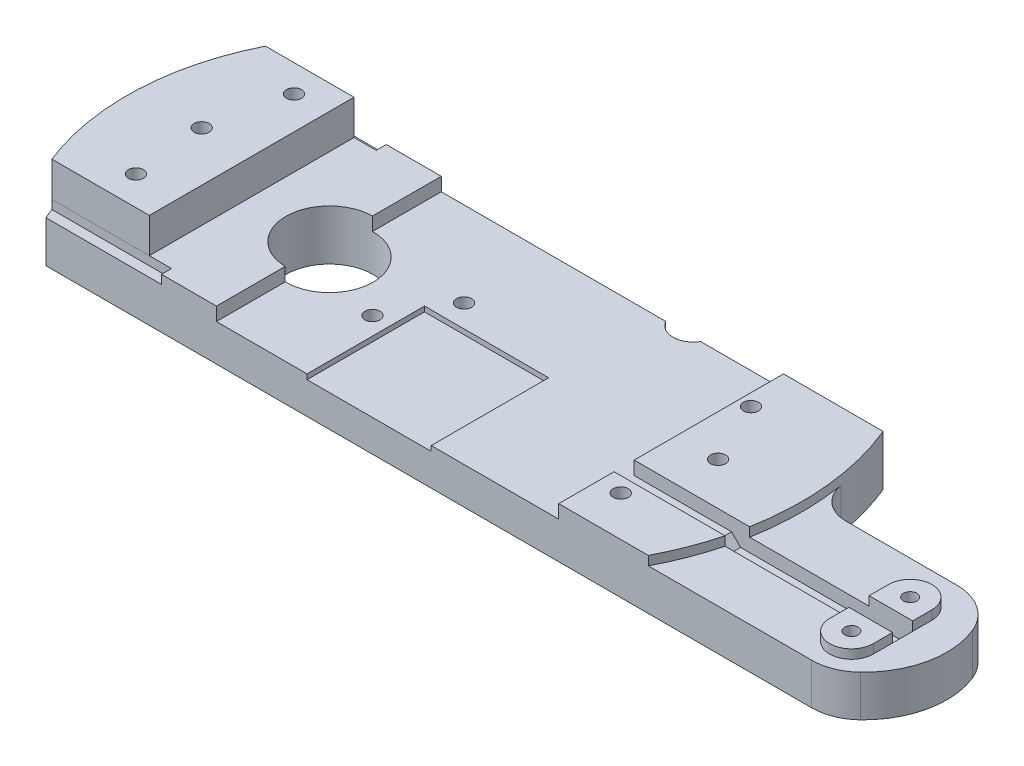
SolidWorks part; units mm, degrees
material "1060 Alloy"
ref_plane "Front Plane" through (0, 0, 0) normal (0, 0, 1) x (1, 0, 0)
ref_plane "Top Plane" through (0, 0, 0) normal (0, 1, 0) x (1, 0, 0)
ref_plane "Right Plane" through (0, 0, 0) normal (1, 0, 0) x (0, 0, -1)
sketch "Sketch1" plane through (0, 0, 0) normal (0, 1, 0) x (1, 0, 0)
  line L1 (-97.5, -33.5) -> (97.5, -33.5)
  line L2 (-97.5, -33.5) -> (-97.5, 33.5)
  line L3 (-97.5, 33.5) -> (97.5, 33.5)
  line L4 (97.5, -33.5) -> (97.5, 33.5)
  line L5 (-97.5, -33.5) -> (97.5, 33.5) construction
  line L6 (-97.5, 33.5) -> (97.5, -33.5) construction
  point P0 (0, 0)
  dimension "D1" = 67
  dimension "D2" = 195
extrude "Boss-Extrude1" add sketch "Sketch1" along normal blind 25.4
sketch "Sketch2" plane through (0, 0, 0) normal (0, -1, 0) x (1, 0, 0)
  line L0 (-97.5, -33.5) -> (-97.5, 33.5) construction
  line L1 (97.5, 33.5) -> (97.5, -33.5) construction
  line L2 (97.5, 33.5) -> (88.5, 33.5)
  line L3 (-97.5, 33.5) -> (97.5, 33.5) construction
  line L4 (97.5, -33.5) -> (91.5, -33.5)
  line L5 (97.5, -33.5) -> (-97.5, -33.5) construction
  line L6 (-97.5, 33.5) -> (-91, 33.5)
  line L7 (-97.5, -33.5) -> (-88, -33.5)
  circle A0 centre (18.0922, -3.2198) radius 79.4078
  circle A1 centre (-22.6589, 2.9929) radius 74.8411
  line M7 (97.5, -33.5) -> (97.5, 33.5)
  line M8 (97.5, 33.5) -> (-97.5, 33.5)
  line M9 (-97.5, 33.5) -> (-97.5, -33.5)
  line M10 (-97.5, -33.5) -> (97.5, -33.5)
  dimension "D1" = 9
  dimension "D2" = 6
  dimension "D3" = 6.5
  dimension "D4" = 9.5
extrude "Cut-Extrude1" cut sketch "Sketch2" against normal through all contours A0 M7 M8 | A0 M10 M7 | A1 M9 M10 | A1 M8 M9 region at (94.8284, 0, 24.4273) region at (95.7123, 0, -25.9883) region at (-95.5654, 0, 25.941) region at (-94.6839, 0, -24.4966)
sketch "Sketch3" plane through (0, 0, 33.5) normal (0, 0, -1) x (-1, 0, 0)
  line L0 (97.5, 25.4) -> (63.2, 25.4)
  line L2 (63.2, 25.4) -> (63.2, 15)
  line L3 (63.2, 15) -> (40.2, 15)
  line L4 (40.2, 15) -> (40.2, 11)
  line L5 (40.2, 11) -> (-61.8, 11)
  line L6 (-91.5, 25.4) -> (88, 25.4) construction
  line L10 (97.5, 0) -> (97.5, 25.4) construction
  line L11 (-61.8, 11) -> (-61.8, 15)
  line L12 (-61.8, 15) -> (-97.5, 15)
  line L13 (-97.5, 25.4) -> (-97.5, 0) construction
  line L14 (-97.5, 15) -> (-97.5, 25.4)
  line L15 (-97.5, 25.4) -> (63.2, 25.4)
  line M13 (-88.5, 0) -> (-88.5, 25.4)
  line M14 (-88.5, 25.4) -> (91, 25.4)
  dimension "D1" = 10.4
  dimension "D2" = 34.3
  dimension "D3" = 23
  dimension "D4" = 4
  dimension "D5" = 102
extrude "Cut-Extrude2" cut sketch "Sketch3" along normal through all contours L11 L12 L2 L3 L4 L5 M13 M14 | L2 L3 L4 L5 L11 L12 L14 L15 region at (12.2699, 18.7206, 33.5)
sketch "Sketch4" plane through (0, 25.4, 0) normal (0, 1, 0) x (1, 0, 0)
  line L0 (-56.5873, 33.5) -> (-56.5873, 30.5)
  line L1 (-63.2, 33.5) -> (-88, 33.5) construction
  line L2 (-56.5873, 30.5) -> (-89.5873, 30.5)
  line L3 (-56.5873, -33.5) -> (-56.5873, -30.5)
  line L4 (-91, -33.5) -> (-63.2, -33.5) construction
  line L5 (-56.5873, -30.5) -> (-92.2617, -30.5)
  line L6 (-56.5873, 33.5) -> (-63.2, 33.5)
  line L7 (-56.5873, -33.5) -> (-63.2, -33.5)
  arc A0 (-88, 33.5) -> (-91, -33.5) centre (-22.6589, -2.9929) ccw construction
  line M5 (-91, -33.5) -> (-63.2, -33.5)
  line M6 (-63.2, -33.5) -> (-63.2, 33.5)
  line M7 (-63.2, 33.5) -> (-88, 33.5)
  arc M8 (-88, 33.5) -> (-91, -33.5) centre (-22.6589, -2.9929) ccw
  dimension "D1" = 3
  dimension "D2" = 3
  dimension "D3" = 33
extrude "Cut-Extrude3" cut sketch "Sketch4" against normal blind 13 contours L2 M6 M7 M8 | L0 L6 L2 M6 | L5 M6 M8 M5 | L7 L3 L5 M6 region at (-59.8937, 25.4, -32) region at (-76.0082, 25.4, -31.9845) region at (-77.4242, 25.4, 31.9889) region at (-59.8937, 25.4, 32)
sketch "Sketch6" plane through (0, 0, 0) normal (0, -1, 0) x (1, 0, 0)
  line L0 (-63.2, -33.5) -> (-97.5, -33.5)
  line L1 (91.5, -33.5) -> (-88, -33.5) construction
  line L2 (-63.2, -33.5) -> (-63.2, 33.5)
  line L3 (-91, 33.5) -> (88.5, 33.5) construction
  line L4 (-63.2, -9) -> (-28.1, -9) construction
  line L5 (-63.2, 8.7) -> (-18.5, 8.7) construction
  line L6 (-63.2, -8.2) -> (-8.1, -8.2) construction
  line L8 (91.5, -33.5) -> (-88, -33.5) construction
  line L9 (-97.5, -33.5) -> (-97.5, 33.5)
  line L10 (-97.5, 33.5) -> (-63.2, 33.5)
  circle A1 centre (-18.5, 8.7) radius 2.25
  circle A2 centre (74.1, -1.7) radius 2.25
  circle A3 centre (68.3, 21.5) radius 2.25
  circle A4 centre (65.4, -20.2) radius 2.25
  circle A5 centre (-8.1, -8.2) radius 2.25
  circle A6 centre (-75.9, 21.8) radius 2.25
  circle A7 centre (-78, 0.1) radius 2.25
  circle A8 centre (-73, -22.4) radius 2.25
  arc A10 (-91, 33.5) -> (-88, -33.5) centre (-22.6589, 2.9929) ccw construction
  dimension "D22" = 4.5
  dimension "D3" = 35.1
  dimension "D4" = 34.3
  dimension "D5" = 44.7
  dimension "D6" = 24.5
  dimension "D7" = 55.1
  dimension "D8" = 42.2
  dimension "D9" = 137.3
  dimension "D10" = 128.6
  dimension "D11" = 131.5
  dimension "D12" = 9.8
  dimension "D13" = 14.8
  dimension "D14" = 12.7
  dimension "D15" = 11.1
  dimension "D16" = 33.6
  dimension "D17" = 55.3
  dimension "D18" = 31.8
  dimension "D19" = 55
  dimension "D20" = 13.3
  dimension "D21" = 25.3
extrude "Cut-Extrude4" cut sketch "Sketch6" against normal through all contours A5 | A1 | A6 | A7 | A8 | A4 | A2 | A3 region at (-18.5, 0, 8.7) region at (74.1, 0, -1.7) region at (68.3, 0, 21.5) region at (65.4, 0, -20.2) region at (-8.1, 0, -8.2) region at (-75.9, 0, 21.8) region at (-78, 0, 0.1) region at (-73, 0, -22.4)
sketch "Sketch7" plane through (0, 11, 0) normal (0, 1, 0) x (1, 0, 0)
  line L1 (-13.2, 1.5) -> (23.8, 1.5)
  line L2 (-13.2, 1.5) -> (-13.2, -33.5)
  line L3 (-13.2, -33.5) -> (23.8, -33.5)
  line L4 (23.8, 1.5) -> (23.8, -33.5)
  line L8 (-63.2, 30.5) -> (-63.2, -30.5) construction
  line L9 (-63.2, 30.5) -> (-63.2, -30.5) construction
  line L10 (-40.2, -33.5) -> (61.8, -33.5) construction
  dimension "D1" = 50
  dimension "D2" = 87
  dimension "D3" = 35
extrude "Cut-Extrude5" cut sketch "Sketch7" against normal blind 1.5
sketch "Sketch8" plane through (0, 25.4, 0) normal (0, 1, 0) x (1, 0, 0)
  line L0 (-56.5873, -33.5) -> (-97.5, -33.5)
  line L1 (-97.5, -33.5) -> (-97.5, 33.5)
  line L3 (-97.5, 33.5) -> (31.9, 33.5)
  line L6 (31.9, 36.5) -> (31.9, 30.5)
  line L7 (31.9, 33.5) -> (37.0962, 33.5)
  line L10 (-56.5873, 33.5) -> (-88, 33.5) construction
  line L11 (-40.2, 33.5) -> (61.8, 33.5) construction
  circle A1 centre (31.9, 36.5) radius 6
  arc A2 (-89.5873, 30.5) -> (-92.2617, -30.5) centre (-22.6589, -2.9929) ccw construction
  dimension "D1" = 12
  dimension "D2" = 129.4
extrude "Cut-Extrude6" cut sketch "Sketch8" against normal blind 18.5 contours L6 A1 L7 | L3 A1 L6 region at (29.8648, 25.4, -32.2699) region at (33.9352, 25.4, -32.2699)
sketch "Sketch9" plane through (0, 0, 0) normal (0, -1, 0) x (1, 0, 0)
  line L0 (88.5, 33.5) -> (137.2004, 33.5)
  line L1 (139.5727, -7.5) -> (97.3846, -7.5)
  arc A0 (153.4738, 1.8643) -> (147.5429, 29.3643) centre (130.3054, 11.2571) ccw
  arc A1 (91.5, -33.5) -> (88.5, 33.5) centre (18.0922, -3.2198) ccw construction
  arc A2 (142.3827, -10.6321) -> (147.5429, 29.3643) centre (130.3054, 11.2571) ccw construction
  arc A3 (147.5429, 29.3643) -> (137.2004, 33.5) centre (137.2004, 18.5) ccw
  arc A4 (147.5429, 29.3643) -> (137.9704, 33.4802) centre (137.2004, 18.5) ccw construction
  arc A5 (139.5727, -7.5) -> (153.4738, 1.8643) centre (139.5727, 7.5) ccw
  circle A6 centre (112.8948, -27.5) radius 16 construction
  circle A7 centre (103.4238, 59.4942) radius 16 construction
  circle A8 centre (112.8948, -27.5) radius 20 construction
  arc A9 (97.3846, -7.5) -> (88.5, 33.5) centre (18.0922, -3.2198) ccw
  circle A10 centre (138.3, 5.25) radius 2
  circle A11 centre (138.3, 22.75) radius 2
  circle A12 centre (138.3, 22.75) radius 2 construction
  circle A13 centre (138.3, 5.25) radius 2 construction
  dimension "D1" = 4
extrude "Boss-Extrude2" add sketch "Sketch9" against normal offset from surface (12.3 mm away) 1.3 up to face at (-16.25, 11, 8.7) offset beyond the face yes
fillet "Fillet1" radius 10 1 edges at (97.3846, 6.15, -7.5)
sketch "Sketch10" plane through (0, 0, 0) normal (0, -1, 0) x (1, 0, 0)
  circle A0 centre (-40.0178, 0) radius 13
  dimension "D1" = 26
extrude "Cut-Extrude7" cut sketch "Sketch10" against normal through all
sketch "Sketch11" plane through (0, 12.3, 0) normal (0, 1, 0) x (1, 0, 0)
  line L0 (138.3, -5.25) -> (138.3, -22.75) construction
  line L1 (144.8, -5.25) -> (144.8, -22.75)
  line L2 (131.8, -5.25) -> (131.8, -22.75)
  line L3 (131.8, -11) -> (144.8, -11)
  line L4 (131.8, -17) -> (144.8, -17)
  line L5 (131.8, -14) -> (144.8, -14) construction
  arc A0 (144.8, -5.25) -> (131.8, -5.25) centre (138.3, -5.25) ccw
  arc A1 (131.8, -22.75) -> (144.8, -22.75) centre (138.3, -22.75) ccw
  point P4 (138.3, -14)
  circle M15 centre (138.3, -22.75) radius 2
  circle M16 centre (138.3, -5.25) radius 2
  dimension "D1" = 13
  dimension "D2" = 6
extrude "Boss-Extrude3" add sketch "Sketch11" along normal up to surface (2.7 mm away) contours L1 A0 L2 L3 M16 | L2 A1 L1 L4 M15 region at (144.6214, 12.3, 8.125) region at (144.6214, 12.3, 19.875) up to face at (70.55, 15, 21.5)
sketch "Sketch12" plane through (0, 0, 11) normal (0, 0, 1) x (1, 0, 0)
  line L0 (144.8, 15) -> (144.8, 8.3)
  line L1 (144.8, 8.3) -> (93.5, 8.3)
  line L3 (97.5, 12.3) -> (88.5, 12.3) construction
  line L4 (90.8, 11) -> (61.8, 11)
  line L5 (61.8, 11) -> (61.8, 15)
  line L6 (61.8, 15) -> (88.5, 15) construction
  line L7 (61.8, 15) -> (144.8, 15)
  line L10 (97.5, 12.3) -> (93.5, 12.3) construction
  line L12 (88.5, 12.3) -> (137.2004, 12.3) construction
  line L13 (93.5, 12.3) -> (93.5, 8.3) construction
  line L14 (61.8, 11) -> (61.8, 15) construction
  line L15 (23.8, 11) -> (61.8, 11) construction
  line L16 (93.5, 8.3) -> (90.8, 11)
  dimension "D1" = 45
extrude "Cut-Extrude8" cut sketch "Sketch12" along normal up to surface (6 mm away) up to face at (138.3, 13.65, 17)
split "Split1" bodies to split 116 resulting bodies 114 115 split by face at (-52.6367, 15, 0)
